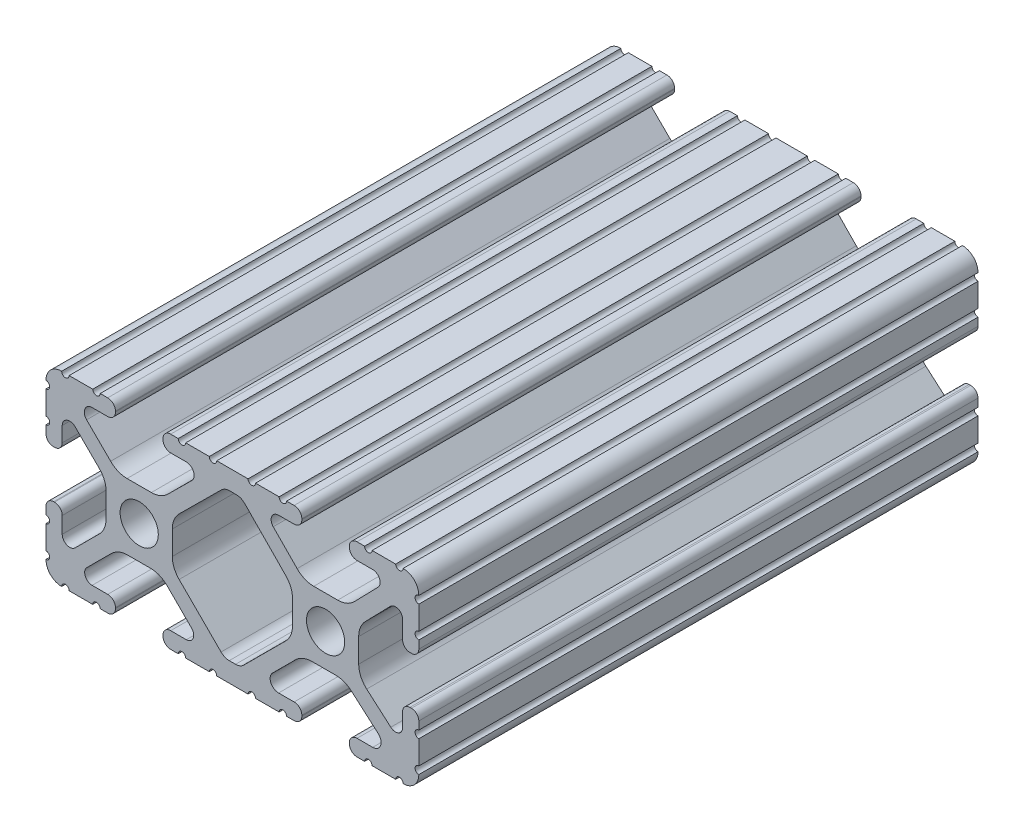
SolidWorks part; units mm, degrees
material "6061 Alloy"
ref_plane "Front Plane" through (0, 0, 0) normal (0, 0, 1) x (1, 0, 0)
ref_plane "Top Plane" through (0, 0, 0) normal (0, 1, 0) x (1, 0, 0)
ref_plane "Right Plane" through (0, 0, 0) normal (1, 0, 0) x (0, 0, -1)
sketch "Sketch1" plane through (0, 0, 0) normal (0, 0, 1) x (1, 0, 0)
  line L0 (-32.9707, 0) -> (32.2708, 0) construction
  line L1 (0, 12.7) -> (0, 0) construction
  line L2 (-12.7, 14.992) -> (-12.7, -12.6999) construction
  line L3 (12.7, 13.9801) -> (12.7, -13.3809) construction
  line L4 (-7.2595, -3.8694) -> (-1.5457, -9.5728)
  line L5 (1.5457, -9.5728) -> (7.2595, -3.8694)
  line L7 (-0.3952, 10.033) -> (0.5515, 10.033)
  line L9 (0.4332, -10.033) -> (-0.4332, -10.033)
  line L12 (8.1915, -1.6223) -> (8.1915, 1.6223)
  line L13 (7.2829, 3.8459) -> (1.6756, 9.5611)
  line L14 (-1.504, 9.5765) -> (-7.252, 3.8768)
  line L15 (-8.1915, 1.6223) -> (-8.1915, -1.6223)
  line L16 (22.2504, 12.7) -> (19.0331, 12.7)
  line L17 (18.0171, 12.7) -> (16.9875, 12.7)
  line L18 (15.9385, 11.651) -> (15.9385, 11.5392)
  line L19 (16.9875, 10.4902) -> (19.1164, 10.4902)
  line L20 (19.8441, 8.7652) -> (16.619, 5.4551)
  line L21 (14.3449, 4.4958) -> (11.0833, 4.4958)
  line L22 (8.817, 5.4472) -> (5.5642, 8.7627)
  line L23 (6.2894, 10.4902) -> (8.4125, 10.4902)
  line L24 (9.4615, 11.5392) -> (9.4615, 11.651)
  line L25 (8.4125, 12.7) -> (7.3829, 12.7)
  line L26 (6.3669, 12.7) -> (3.1496, 12.7)
  line L27 (2.1336, 12.7) -> (-2.1336, 12.7)
  line L28 (-3.1496, 12.7) -> (-6.3669, 12.7)
  line L29 (-7.3829, 12.7) -> (-8.4125, 12.7)
  line L30 (-9.4615, 11.651) -> (-9.4615, 11.5392)
  line L31 (-8.4125, 10.4902) -> (-6.2836, 10.4902)
  line L32 (-5.5326, 8.6661) -> (-8.81, 5.4163)
  line L33 (-11.0455, 4.4958) -> (-14.3545, 4.4958)
  line L34 (-16.59, 5.4163) -> (-19.8674, 8.6661)
  line L35 (-19.1164, 10.4902) -> (-16.9875, 10.4902)
  line L36 (-15.9385, 11.5392) -> (-15.9385, 11.651)
  line L37 (-16.9875, 12.7) -> (-18.0171, 12.7)
  line L38 (-19.0331, 12.7) -> (-22.2504, 12.7)
  line L39 (-25.4, 9.5504) -> (-25.4, 6.3331)
  line L40 (-25.4, 5.3171) -> (-25.4, 4.2375)
  line L41 (-24.401, 3.2385) -> (-24.2392, 3.2385)
  line L42 (-23.1902, 4.2875) -> (-23.1902, 6.3347)
  line L43 (-21.434, 7.0665) -> (-18.148, 3.8082)
  line L44 (-17.2085, 1.5536) -> (-17.2085, -1.6952)
  line L45 (-18.1405, -3.9423) -> (-21.4316, -7.2274)
  line L46 (-23.1902, -6.498) -> (-23.1902, -4.2875)
  line L47 (-24.2392, -3.2385) -> (-24.351, -3.2385)
  line L48 (-25.4, -4.2875) -> (-25.4, -5.3171)
  line L49 (-25.4, -6.3331) -> (-25.4, -9.5504)
  line L50 (-22.2504, -12.7) -> (-19.0331, -12.7)
  line L51 (-18.0171, -12.7) -> (-16.9875, -12.7)
  line L52 (-15.9384, -11.651) -> (-15.9384, -11.5392)
  line L53 (-16.9875, -10.4902) -> (-19.1164, -10.4902)
  line L54 (-19.8341, -8.7551) -> (-16.4966, -5.4237)
  line L55 (-14.2536, -4.4958) -> (-11.1464, -4.4958)
  line L56 (-8.9034, -5.4237) -> (-5.5659, -8.7551)
  line L57 (-6.2836, -10.4902) -> (-8.4125, -10.4902)
  line L58 (-9.4616, -11.5392) -> (-9.4616, -11.651)
  line L59 (-8.4125, -12.7) -> (-7.3829, -12.7)
  line L60 (-6.3669, -12.7) -> (-3.1496, -12.7)
  line L61 (-2.1336, -12.7) -> (2.1336, -12.7)
  line L62 (3.1496, -12.7) -> (6.3669, -12.7)
  line L63 (7.3829, -12.7) -> (8.4125, -12.7)
  line L64 (9.4616, -11.651) -> (9.4616, -11.5392)
  line L65 (8.4125, -10.4902) -> (6.2894, -10.4902)
  line L66 (5.4807, -8.5353) -> (8.5979, -5.4237)
  line L67 (10.8409, -4.4958) -> (14.1026, -4.4958)
  line L68 (16.1879, -5.2766) -> (19.8682, -8.4822)
  line L69 (19.1164, -10.4902) -> (16.9875, -10.4902)
  line L70 (15.9384, -11.5392) -> (15.9384, -11.651)
  line L71 (16.9875, -12.7) -> (18.0171, -12.7)
  line L72 (19.0331, -12.7) -> (22.2504, -12.7)
  line L73 (25.4, -9.5504) -> (25.4, -6.3331)
  line L74 (25.4, -5.3171) -> (25.4, -4.2375)
  line L75 (24.401, -3.2385) -> (24.1892, -3.2385)
  line L76 (23.1902, -4.2375) -> (23.1902, -6.1559)
  line L77 (21.584, -6.8869) -> (18.2982, -4.025)
  line L78 (17.2085, -1.6308) -> (17.2085, 1.6308)
  line L79 (18.1094, 3.8465) -> (21.5263, 7.3534)
  line L80 (23.1902, 6.6769) -> (23.1902, 4.2375)
  line L81 (24.1892, 3.2385) -> (24.401, 3.2385)
  line L82 (25.4, 4.2375) -> (25.4, 5.3171)
  line L83 (25.4, 6.3332) -> (25.4, 9.5504)
  circle A0 centre (-12.7, 0) radius 2.6035
  circle A1 centre (12.7, 0) radius 2.6035
  arc A2 (-0.3952, 10.033) -> (-1.504, 9.5765) centre (-0.3952, 8.4582) ccw
  arc A3 (0.5515, 10.033) -> (1.6756, 9.5611) centre (0.5515, 8.4582) cw
  arc A4 (-8.1915, -1.6223) -> (-7.2595, -3.8694) centre (-5.0165, -1.6223) ccw
  arc A5 (-0.4332, -10.033) -> (-1.5457, -9.5728) centre (-0.4332, -8.4582) cw
  arc A6 (7.2595, -3.8694) -> (8.1915, -1.6223) centre (5.0165, -1.6223) ccw
  arc A7 (8.1915, 1.6223) -> (7.2829, 3.8459) centre (5.0165, 1.6223) ccw
  arc A8 (0.4332, -10.033) -> (1.5457, -9.5728) centre (0.4332, -8.4582) ccw
  arc A9 (-7.252, 3.8768) -> (-8.1915, 1.6223) centre (-5.0165, 1.6223) ccw
  arc A16 (25.3998, 10.5664) -> (23.2664, 12.6998) centre (23.2918, 10.5918) ccw
  arc A17 (22.2504, 12.7) -> (23.2664, 12.6998) centre (22.7584, 12.7) ccw
  arc A18 (18.0171, 12.7) -> (19.0331, 12.7) centre (18.5251, 12.7) ccw
  arc A19 (16.9875, 12.7) -> (15.9385, 11.651) centre (16.9875, 11.651) ccw
  arc A20 (15.9385, 11.5392) -> (16.9875, 10.4902) centre (16.9875, 11.5392) ccw
  arc A21 (19.8441, 8.7652) -> (19.1164, 10.4902) centre (19.1164, 9.4742) ccw
  arc A22 (14.3449, 4.4958) -> (16.619, 5.4551) centre (14.3449, 7.6708) ccw
  arc A23 (8.817, 5.4472) -> (11.0833, 4.4958) centre (11.0833, 7.6708) ccw
  arc A24 (6.2894, 10.4902) -> (5.5642, 8.7627) centre (6.2894, 9.4742) ccw
  arc A25 (8.4125, 10.4902) -> (9.4615, 11.5392) centre (8.4125, 11.5392) ccw
  arc A26 (9.4615, 11.651) -> (8.4125, 12.7) centre (8.4125, 11.651) ccw
  arc A27 (6.3669, 12.7) -> (7.3829, 12.7) centre (6.8749, 12.7) ccw
  arc A28 (2.1336, 12.7) -> (3.1496, 12.7) centre (2.6416, 12.7) ccw
  arc A29 (-3.1496, 12.7) -> (-2.1336, 12.7) centre (-2.6416, 12.7) ccw
  arc A30 (-7.3829, 12.7) -> (-6.3669, 12.7) centre (-6.8749, 12.7) ccw
  arc A31 (-8.4125, 12.7) -> (-9.4615, 11.651) centre (-8.4125, 11.651) ccw
  arc A32 (-9.4615, 11.5392) -> (-8.4125, 10.4902) centre (-8.4125, 11.5392) ccw
  arc A33 (-5.5326, 8.6661) -> (-6.2836, 10.4902) centre (-6.2836, 9.4235) ccw
  arc A34 (-11.0455, 4.4958) -> (-8.81, 5.4163) centre (-11.0455, 7.6708) ccw
  arc A35 (-16.59, 5.4163) -> (-14.3545, 4.4958) centre (-14.3545, 7.6708) ccw
  arc A36 (-19.1164, 10.4902) -> (-19.8674, 8.6661) centre (-19.1164, 9.4235) ccw
  arc A37 (-16.9875, 10.4902) -> (-15.9385, 11.5392) centre (-16.9875, 11.5392) ccw
  arc A38 (-15.9385, 11.651) -> (-16.9875, 12.7) centre (-16.9875, 11.651) ccw
  arc A39 (-19.0331, 12.7) -> (-18.0171, 12.7) centre (-18.5251, 12.7) ccw
  arc A40 (-23.2664, 12.6998) -> (-22.2504, 12.7) centre (-22.7584, 12.7) ccw
  arc A41 (-23.2664, 12.6998) -> (-25.3998, 10.5664) centre (-23.2918, 10.5918) ccw
  arc A42 (-25.4, 9.5504) -> (-25.3998, 10.5664) centre (-25.4, 10.0584) ccw
  arc A43 (-25.4, 5.3171) -> (-25.4, 6.3331) centre (-25.4, 5.8251) ccw
  arc A44 (-25.4, 4.2375) -> (-24.401, 3.2385) centre (-24.401, 4.2375) ccw
  arc A45 (-24.2392, 3.2385) -> (-23.1902, 4.2875) centre (-24.2392, 4.2875) ccw
  arc A46 (-21.434, 7.0665) -> (-23.1902, 6.3347) centre (-22.1596, 6.3347) ccw
  arc A47 (-17.2085, 1.5536) -> (-18.148, 3.8082) centre (-20.3835, 1.5536) ccw
  arc A48 (-18.1405, -3.9423) -> (-17.2085, -1.6952) centre (-20.3835, -1.6952) ccw
  arc A49 (-23.1902, -6.498) -> (-21.4316, -7.2274) centre (-22.1596, -6.498) ccw
  arc A50 (-23.1902, -4.2875) -> (-24.2392, -3.2385) centre (-24.2392, -4.2875) ccw
  arc A51 (-24.351, -3.2385) -> (-25.4, -4.2875) centre (-24.351, -4.2875) ccw
  arc A52 (-25.4, -6.3331) -> (-25.4, -5.3171) centre (-25.4, -5.8251) ccw
  arc A53 (-25.3998, -10.5664) -> (-25.4, -9.5504) centre (-25.4, -10.0584) ccw
  arc A54 (-25.3998, -10.5664) -> (-23.2664, -12.6998) centre (-23.2918, -10.5918) ccw
  arc A55 (-22.2504, -12.7) -> (-23.2664, -12.6998) centre (-22.7584, -12.7) ccw
  arc A56 (-18.0171, -12.7) -> (-19.0331, -12.7) centre (-18.5251, -12.7) ccw
  arc A57 (-16.9875, -12.7) -> (-15.9384, -11.651) centre (-16.9875, -11.651) ccw
  arc A58 (-15.9384, -11.5392) -> (-16.9875, -10.4902) centre (-16.9875, -11.5392) ccw
  arc A59 (-19.8341, -8.7551) -> (-19.1164, -10.4902) centre (-19.1164, -9.4742) ccw
  arc A60 (-14.2536, -4.4958) -> (-16.4966, -5.4237) centre (-14.2536, -7.6708) ccw
  arc A61 (-8.9034, -5.4237) -> (-11.1464, -4.4958) centre (-11.1464, -7.6708) ccw
  arc A62 (-6.2836, -10.4902) -> (-5.5659, -8.7551) centre (-6.2836, -9.4742) ccw
  arc A63 (-8.4125, -10.4902) -> (-9.4616, -11.5392) centre (-8.4125, -11.5392) ccw
  arc A64 (-9.4616, -11.651) -> (-8.4125, -12.7) centre (-8.4125, -11.651) ccw
  arc A65 (-6.3669, -12.7) -> (-7.3829, -12.7) centre (-6.8749, -12.7) ccw
  arc A66 (-2.1336, -12.7) -> (-3.1496, -12.7) centre (-2.6416, -12.7) ccw
  arc A67 (3.1496, -12.7) -> (2.1336, -12.7) centre (2.6416, -12.7) ccw
  arc A68 (7.3829, -12.7) -> (6.3669, -12.7) centre (6.8749, -12.7) ccw
  arc A69 (8.4125, -12.7) -> (9.4616, -11.651) centre (8.4125, -11.651) ccw
  arc A70 (9.4616, -11.5392) -> (8.4125, -10.4902) centre (8.4125, -11.5392) ccw
  arc A71 (5.4807, -8.5353) -> (6.2894, -10.4902) centre (6.2894, -9.3455) ccw
  arc A72 (10.8409, -4.4958) -> (8.5979, -5.4237) centre (10.8409, -7.6708) ccw
  arc A73 (16.1879, -5.2766) -> (14.1026, -4.4958) centre (14.1026, -7.6708) ccw
  arc A74 (19.1164, -10.4902) -> (19.8682, -8.4822) centre (19.1164, -9.3455) ccw
  arc A75 (16.9875, -10.4902) -> (15.9384, -11.5392) centre (16.9875, -11.5392) ccw
  arc A76 (15.9384, -11.651) -> (16.9875, -12.7) centre (16.9875, -11.651) ccw
  arc A77 (19.0331, -12.7) -> (18.0171, -12.7) centre (18.5251, -12.7) ccw
  arc A78 (23.2664, -12.6998) -> (22.2504, -12.7) centre (22.7584, -12.7) ccw
  arc A79 (23.2664, -12.6998) -> (25.3998, -10.5664) centre (23.2918, -10.5918) ccw
  arc A80 (25.4, -9.5504) -> (25.3998, -10.5664) centre (25.4, -10.0584) ccw
  arc A81 (25.4, -5.3171) -> (25.4, -6.3331) centre (25.4, -5.8251) ccw
  arc A82 (25.4, -4.2375) -> (24.401, -3.2385) centre (24.401, -4.2375) ccw
  arc A83 (24.1892, -3.2385) -> (23.1902, -4.2375) centre (24.1892, -4.2375) ccw
  arc A84 (21.584, -6.8869) -> (23.1902, -6.1559) centre (22.2207, -6.1559) ccw
  arc A85 (17.2085, -1.6308) -> (18.2982, -4.025) centre (20.3835, -1.6308) ccw
  arc A86 (18.1094, 3.8465) -> (17.2085, 1.6308) centre (20.3835, 1.6308) ccw
  arc A87 (23.1902, 6.6769) -> (21.5263, 7.3534) centre (22.2207, 6.6769) ccw
  arc A88 (23.1902, 4.2375) -> (24.1892, 3.2385) centre (24.1892, 4.2375) ccw
  arc A89 (24.401, 3.2385) -> (25.4, 4.2375) centre (24.401, 4.2375) ccw
  arc A90 (25.4, 6.3332) -> (25.4, 5.3171) centre (25.4, 5.8251) ccw
  arc A91 (25.3998, 10.5664) -> (25.4, 9.5504) centre (25.4, 10.0584) ccw
  dimension "D1" = 5.207
  dimension "D6" = 6.477
  dimension "D7" = 14.859
  dimension "D14" = 1.5748
  dimension "D16" = 1.5748
  dimension "D15" = 3.175
  dimension "D2" = 25.4
  dimension "D3" = 50.8
  dimension "D4" = 25.4
  dimension "D5" = 8.2042
  dimension "D8" = 2.2098
  dimension "D9" = 2.2098
  dimension "D10" = 2.2098
  dimension "D11" = 2.2098
  dimension "D12" = 2.2098
  dimension "D13" = 6.477
extrude "Extrude1" add sketch "Sketch1" against normal blind 76.2
